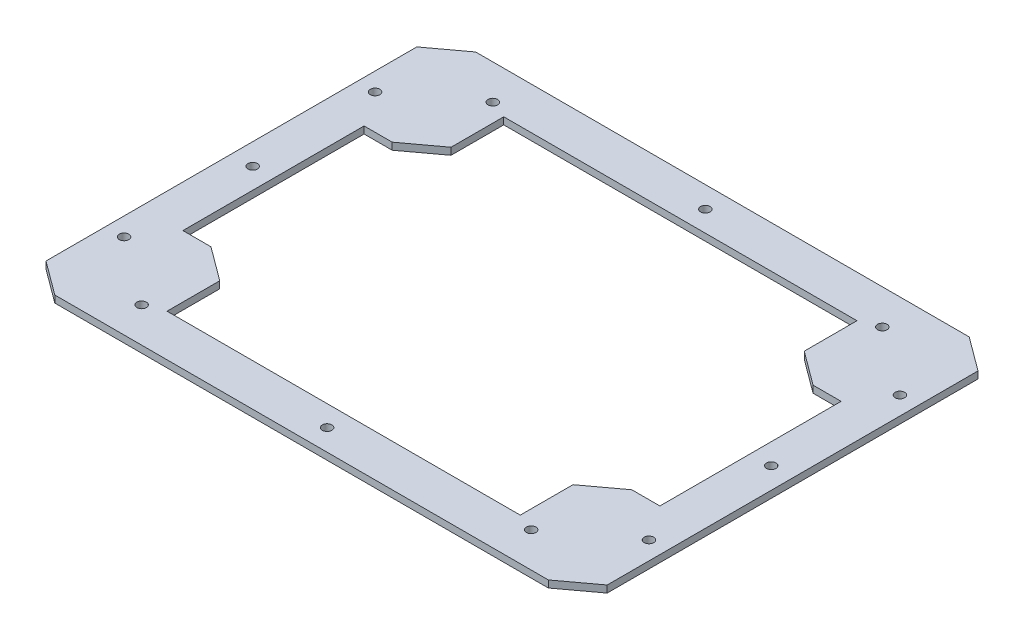
SolidWorks part; units mm, degrees
material "Thornel Mat VMA"
ref_plane "Front Plane" through (0, 0, 0) normal (0, 0, 1) x (1, 0, 0)
ref_plane "Top Plane" through (0, 0, 0) normal (0, 1, 0) x (1, 0, 0)
ref_plane "Right Plane" through (0, 0, 0) normal (1, 0, 0) x (0, 0, -1)
sketch "Sketch1" plane through (0, 0, 0) normal (0, 1, 0) x (1, 0, 0)
  line L0 (-127, 83.9186) -> (-111.6865, 95.25)
  line L1 (-127, -95.25) -> (127, -95.25)
  line L2 (-127, -95.25) -> (-127, 95.25)
  line L3 (-127, 95.25) -> (127, 95.25)
  line L4 (127, -95.25) -> (127, 95.25)
  line L5 (-107.95, 41.011) -> (-107.95, -41.011)
  line L8 (-107.95, 41.011) -> (-95.25, 41.011)
  line L10 (-127, 95.25) -> (127, -95.25) construction
  line L12 (127, 83.9186) -> (111.6865, 95.25)
  line L14 (79.9365, 52.3423) -> (79.9365, 76.2)
  line L15 (95.25, 41.011) -> (79.9365, 52.3423)
  line L16 (107.95, 41.011) -> (95.25, 41.011)
  line L17 (107.95, 41.011) -> (107.95, -41.011)
  line L18 (127, -83.9186) -> (111.6865, -95.25)
  line L19 (107.95, -41.011) -> (95.25, -41.011)
  line L20 (95.25, -41.011) -> (79.9365, -52.3423)
  line L21 (79.9365, -52.3423) -> (79.9365, -76.2)
  line L22 (127, 0) -> (-127, 0) construction
  line L23 (0, -13.6985) -> (0, 95.25) construction
  line L26 (-79.9365, -52.3423) -> (-79.9365, -76.2)
  line L27 (-95.25, 41.011) -> (-127, 83.9186) construction
  line L28 (-95.25, 41.011) -> (-79.9365, 52.3423)
  line L29 (-79.9365, 52.3423) -> (-79.9365, 76.2)
  line L31 (-95.25, -41.011) -> (-79.9365, -52.3423)
  line L32 (-107.95, -41.011) -> (-95.25, -41.011)
  line L33 (-127, -83.9186) -> (-111.6865, -95.25)
  line L34 (-79.9365, 52.3423) -> (-111.6865, 95.25) construction
  line L36 (-79.9365, 76.2) -> (79.9365, 76.2)
  line L37 (38.8318, 76.2) -> (79.9365, 76.2)
  line L38 (-79.9365, -76.2) -> (79.9365, -76.2)
  line L39 (38.1, -76.2) -> (79.9365, -76.2)
  point P0 (0, 0)
  point P1 (0, 0)
  point P14 (0, 0)
  point P22 (0, 76.2)
  point P33 (107.95, 0)
  point P41 (0, 0)
  point P44 (-107.95, 0)
  point P45 (-38.1, 0)
  point P46 (-31.75, 0)
  dimension "D1" = 190.5
  dimension "D2" = 254
  dimension "D3" = 19.05
  dimension "D4" = 19.05
  dimension "D5" = 143.5
  dimension "D6" = 19.05
  dimension "D7" = 12.7
extrude "Boss-Extrude1" add sketch "Sketch1" along normal blind 3.175 contours L2 L1 L4 L3 L8 region at (-117.4547, 0, -87.0321)
sketch "Sketch2" plane through (0, 3.175, 0) normal (0, 1, 0) x (1, 0, 0)
  line L0 (-87.5933, 46.6767) -> (-119.3433, 89.5843) construction
  line L1 (-95.25, 41.011) -> (-79.9365, 52.3423) construction
  line L2 (-127, 83.9186) -> (-111.6865, 95.25) construction
  line L3 (0, 0) -> (0, 95.25) construction
  line L4 (-111.6865, 95.25) -> (111.6865, 95.25) construction
  line L5 (0, 0) -> (-127, 0) construction
  line L6 (-127, -83.9186) -> (-127, 83.9186) construction
  line L7 (-103.4683, 68.1305) -> (-88.1548, 79.4619) construction
  line L9 (-111.6865, -95.25) -> (111.6865, -95.25) construction
  circle A0 centre (-88.1548, 79.4619) radius 2.159
  circle A1 centre (88.1548, 79.4619) radius 2.159
  circle A2 centre (88.1548, -79.4619) radius 2.159
  circle A3 centre (-88.1548, -79.4619) radius 2.159
  circle A4 centre (-118.7817, 56.7991) radius 2.159
  circle A5 centre (118.7817, 56.7991) radius 2.159
  circle A6 centre (-118.7817, -56.7991) radius 2.159
  circle A7 centre (118.7817, -56.7991) radius 2.159
  circle A8 centre (1.9277, -85.598) radius 2.159
  circle A9 centre (1.9277, 85.598) radius 2.159
  circle A10 centre (-117.348, -0.0205) radius 2.159
  circle A11 centre (117.348, -0.0205) radius 2.159
  dimension "D2" = 4.318
  dimension "D3" = 9.652
  dimension "D1" = 19.05
  dimension "D4" = 9.652
extrude "Cut-Extrude1" cut sketch "Sketch2" against normal through all
